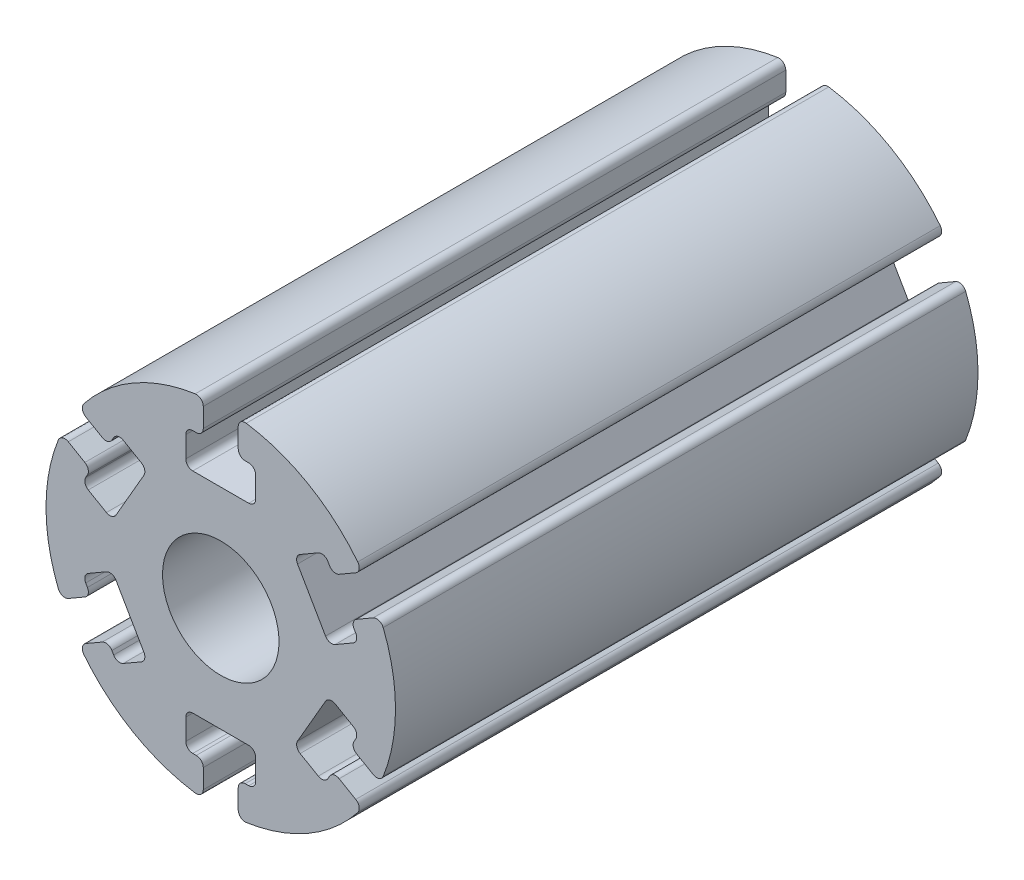
SolidWorks part; units mm, degrees
other "Marcação1"
sketch "Esboço6" plane through (-5, 5.7735, 12.5) normal (-0.9372, 0.3304, 0.1115) x (0.1181, 0, 0.993)
ref_plane "Plano frontal" through (0, 0, 0) normal (0, 0, 1) x (1, 0, 0)
ref_plane "Plano superior" through (0, 0, 0) normal (0, 1, 0) x (1, 0, 0)
ref_plane "Plano direito" through (0, 0, 0) normal (1, 0, 0) x (0, 0, -1)
sketch "Esboço1" plane through (0, 0, 0) normal (0, 0, 1) x (1, 0, 0)
  circle A0 centre (0, 0) radius 2.5 construction
  circle A2 centre (0, 0) radius 7.5
  dimension "D1" = 5
  dimension "D2" = 15
extrude "Ressalto-extrusão1" add sketch "Esboço1" along normal mid plane 25
sketch "Esboço7" plane through (0, 0, 12.5) normal (0, 0, -1) x (-1, 0, 0)
  circle A0 centre (0, 0) radius 2.5
  dimension "D1" = 5
extrude "Corte-extrusão1" cut sketch "Esboço7" along normal blind 16
sketch "Esboço9" plane through (0, 0, 12.5) normal (0, 0, 1) x (1, 0, 0)
  line L0 (-0.75, 6) -> (-0.75, 7.5)
  line L1 (-0.75, 7.5) -> (0.75, 7.5)
  line L2 (-1.5, 6) -> (-0.75, 6)
  line L3 (-1.5, 6) -> (-1.5, 4.5)
  line L4 (-1.5, 4.5) -> (1.5, 4.5)
  line L5 (1.5, 6) -> (1.5, 4.5)
  line L6 (0.75, 6) -> (1.5, 6)
  line L7 (0.75, 6) -> (0.75, 7.5)
  line L8 (4.4462, 4.299) -> (3.1471, 3.549)
  line L9 (4.4462, 4.299) -> (4.8212, 3.6495)
  line L10 (4.8212, 3.6495) -> (6.1202, 4.3995)
  line L11 (6.1202, 4.3995) -> (6.8702, 3.1005)
  line L12 (5.5712, 2.3505) -> (6.8702, 3.1005)
  line L13 (5.5712, 2.3505) -> (5.9462, 1.701)
  line L14 (5.9462, 1.701) -> (4.6471, 0.951)
  line L15 (3.1471, 3.549) -> (4.6471, 0.951)
  line L16 (5.9462, -1.701) -> (4.6471, -0.951)
  line L17 (5.9462, -1.701) -> (5.5712, -2.3505)
  line L18 (5.5712, -2.3505) -> (6.8702, -3.1005)
  line L19 (6.8702, -3.1005) -> (6.1202, -4.3995)
  line L20 (4.8212, -3.6495) -> (6.1202, -4.3995)
  line L21 (4.8212, -3.6495) -> (4.4462, -4.299)
  line L22 (4.4462, -4.299) -> (3.1471, -3.549)
  line L23 (4.6471, -0.951) -> (3.1471, -3.549)
  line L24 (1.5, -6) -> (1.5, -4.5)
  line L25 (1.5, -6) -> (0.75, -6)
  line L26 (0.75, -6) -> (0.75, -7.5)
  line L27 (0.75, -7.5) -> (-0.75, -7.5)
  line L28 (-0.75, -6) -> (-0.75, -7.5)
  line L29 (-0.75, -6) -> (-1.5, -6)
  line L30 (-1.5, -6) -> (-1.5, -4.5)
  line L31 (1.5, -4.5) -> (-1.5, -4.5)
  line L32 (-4.4462, -4.299) -> (-3.1471, -3.549)
  line L33 (-4.4462, -4.299) -> (-4.8212, -3.6495)
  line L34 (-4.8212, -3.6495) -> (-6.1202, -4.3995)
  line L35 (-6.1202, -4.3995) -> (-6.8702, -3.1005)
  line L36 (-5.5712, -2.3505) -> (-6.8702, -3.1005)
  line L37 (-5.5712, -2.3505) -> (-5.9462, -1.701)
  line L38 (-5.9462, -1.701) -> (-4.6471, -0.951)
  line L39 (-3.1471, -3.549) -> (-4.6471, -0.951)
  line L40 (-5.9462, 1.701) -> (-4.6471, 0.951)
  line L41 (-5.9462, 1.701) -> (-5.5712, 2.3505)
  line L42 (-5.5712, 2.3505) -> (-6.8702, 3.1005)
  line L43 (-6.8702, 3.1005) -> (-6.1202, 4.3995)
  line L44 (-4.8212, 3.6495) -> (-6.1202, 4.3995)
  line L45 (-4.8212, 3.6495) -> (-4.4462, 4.299)
  line L46 (-4.4462, 4.299) -> (-3.1471, 3.549)
  line L47 (-4.6471, 0.951) -> (-3.1471, 3.549)
  circle A0 centre (0, 0) radius 7.5 construction
  point P7 (0, 7.5)
  point P55 (0, 0)
  dimension "D1" = 1.5
  dimension "D2" = 3
  dimension "D3" = 3
  dimension "D4" = 1.5
  dimension "D5" = 6
extrude "Corte-extrusão2" cut sketch "Esboço9" against normal through all
fillet "Filete2" radius 0.3 48 edges at (0.75, 7.4624, 0) (6.0876, 4.3807, 0) (4.8212, 3.6495, 0) (4.4462, 4.299, 0) (3.1471, 3.549, 0) (4.6471, 0.951, 0) (5.9462, 1.701, 0) (5.5712, 2.3505, 0) (6.8376, 3.0817, 0) (6.8376, -3.0817, 0) (5.5712, -2.3505, 0) (5.9462, -1.701, 0) (4.6471, -0.951, 0) (3.1471, -3.549, 0) (4.4462, -4.299, 0) (4.8212, -3.6495, 0) (6.0876, -4.3807, 0) (0.75, -7.4624, 0) (0.75, -6, 0) (1.5, -6, 0) (1.5, -4.5, 0) (-1.5, -4.5, 0) (-1.5, -6, 0) (-0.75, -6, 0) (-0.75, -7.4624, 0) (-6.0876, -4.3807, 0) (-4.8212, -3.6495, 0) (-4.4462, -4.299, 0) (-3.1471, -3.549, 0) (-4.6471, -0.951, 0) (-5.9462, -1.701, 0) (-5.5712, -2.3505, 0) (-6.8376, -3.0817, 0) (-6.8376, 3.0817, 0) (-5.5712, 2.3505, 0) (-5.9462, 1.701, 0) (-4.6471, 0.951, 0) (-3.1471, 3.549, 0) (-4.4462, 4.299, 0) (-4.8212, 3.6495, 0) (-6.0876, 4.3807, 0) (-0.75, 7.4624, 0) (-0.75, 6, 0) (-1.5, 6, 0) (1.5, 6, 0) (0.75, 6, 0) (1.5, 4.5, 0) (-1.5, 4.5, 0)
sketch "Esboço10" plane through (0, 0, 0) normal (0, 1, 0) x (1, 0, 0)
  line L0 (-5.8789, -12.5) -> (-1.0937, -12.5) construction
  circle A0 centre (0, -6) radius 2.5
  dimension "D2" = 5
  dimension "D1" = 6.5
extrude "Corte-extrusão3" cut sketch "Esboço10" against normal blind 10
move or copy body "Corpo-Converter em corpo de malha1" [suppressed] bodies to move or copy 107 copy no translate (0, 0, 0) parameters "D1"=0, "D2"=0, "D3"=0
